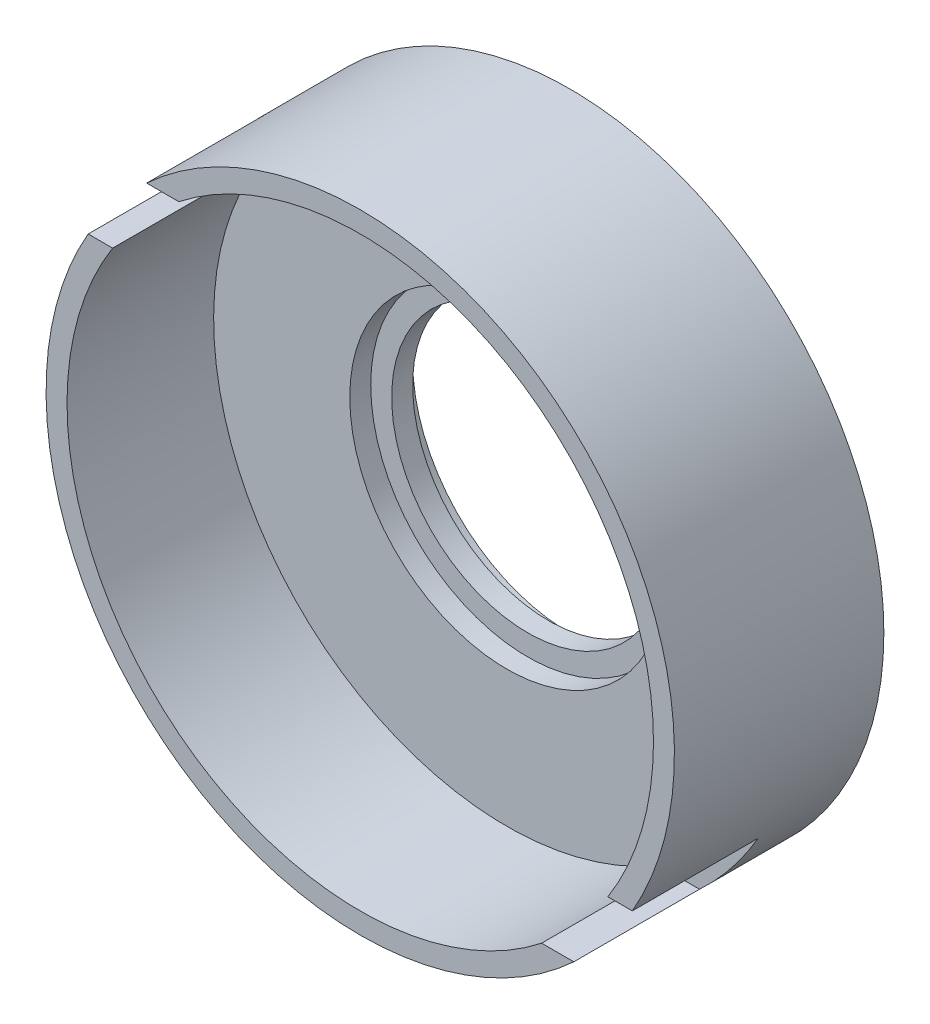
SolidWorks part; units mm, degrees
ref_plane "Спереди" through (0, 0, 0) normal (0, 0, 1) x (1, 0, 0)
ref_plane "Сверху" through (0, 0, 0) normal (0, 1, 0) x (1, 0, 0)
ref_plane "Справа" through (0, 0, 0) normal (1, 0, 0) x (0, 0, -1)
sketch "Эскиз5" plane through (0, 0, 0) normal (0, 0, 1) x (1, 0, 0)
  circle A0 centre (0, 0) radius 30
  dimension "D1" = 60
extrude "Бобышка-Вытянуть1" add sketch "Эскиз5" along normal blind 20
sketch "Эскиз6" plane through (0, 0, 0) normal (0, 0, 1) x (1, 0, 0)
  circle A0 centre (0, 0) radius 28
  dimension "D1" = 56
extrude "Вырез-Вытянуть1" cut sketch "Эскиз6" along normal blind 14 from offset 6
sketch "Эскиз7" plane through (0, 0, 0) normal (0, 0, 1) x (1, 0, 0)
  circle A0 centre (0, 0) radius 13
  dimension "D1" = 26
extrude "Вырез-Вытянуть2" cut sketch "Эскиз7" along normal blind 15
sketch "Эскиз8" plane through (0, 0, 0) normal (0, 0, 1) x (1, 0, 0)
  circle A0 centre (0, 0) radius 15
  dimension "D1" = 30
extrude "Вырез-Вытянуть3" cut sketch "Эскиз8" along normal blind 16 from offset 4
sketch "Эскиз10" plane through (0, 0, 0) normal (0, 0, 1) x (1, 0, 0)
  line L1 (-30, 15) -> (-15, 15)
  line L2 (-30, 15) -> (-30, 22)
  line L3 (-30, 22) -> (-15, 22)
  line L4 (-15, 15) -> (-15, 22)
  dimension "D1" = 15
  dimension "D2" = 15
  dimension "D3" = 7
  dimension "D4" = 15
extrude "Вырез-Вытянуть4" cut sketch "Эскиз10" along normal blind 12 from offset 8
sketch "Эскиз13" plane through (0, 0, 0) normal (0, 0, 1) x (1, 0, 0)
  line L1 (15, -15) -> (30, -15)
  line L2 (15, -15) -> (15, -22)
  line L3 (15, -22) -> (30, -22)
  line L4 (30, -15) -> (30, -22)
  dimension "D1" = 15
  dimension "D2" = 15
  dimension "D3" = 15
  dimension "D4" = 7
extrude "Вырез-Вытянуть5" cut sketch "Эскиз13" along normal blind 12 from offset 8
sketch "Эскиз14" plane through (0, 0, 0) normal (0, 0, 1) x (1, 0, 0)
  circle A0 centre (0, 0) radius 15
  dimension "D1" = 30
extrude "Вырез-Вытянуть6" cut sketch "Эскиз14" along normal blind 2
